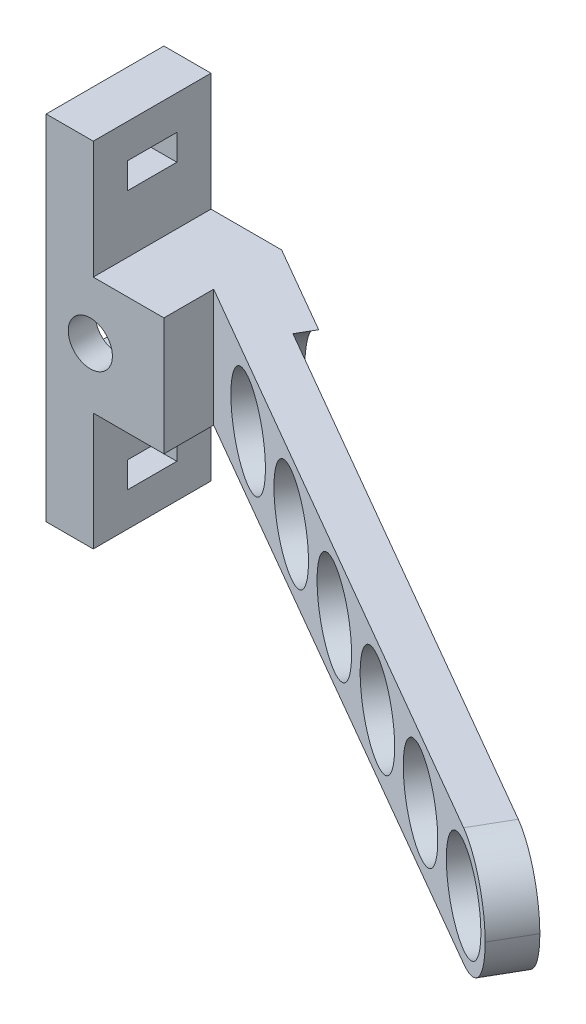
SolidWorks part; units mm, degrees
ref_plane "Front Plane" through (0, 0, 0) normal (0, 0, 1) x (1, 0, 0)
ref_plane "Top Plane" through (0, 0, 0) normal (0, 1, 0) x (1, 0, 0)
ref_plane "Right Plane" through (0, 0, 0) normal (1, 0, 0) x (0, 0, -1)
sketch "Sketch1" plane through (0, 0, 0) normal (0, 0, 1) x (1, 0, 0)
  line L1 (0, 0) -> (-12.7, 0)
  line L2 (0, 0) -> (0, 12.7)
  line L3 (0, 12.7) -> (-12.7, 12.7)
  line L4 (-12.7, 0) -> (-12.7, 12.7)
  dimension "D1" = 12.7
  dimension "D2" = 12.7
extrude "Boss-Extrude1" add sketch "Sketch1" along normal blind 12.7
sketch "Sketch2" plane through (-12.7, 0, 0) normal (-1, 0, 0) x (0, 0, 1)
  line L1 (0, 12.7) -> (12.7, 12.7)
  line L2 (0, 12.7) -> (0, 25.4)
  line L3 (0, 25.4) -> (12.7, 25.4)
  line L4 (12.7, 12.7) -> (12.7, 25.4)
  line L5 (12.7, 12.7) -> (12.7, 0) construction
  line L6 (0, 6.35) -> (12.7, 6.35) construction
  line L7 (3.683, 18.923) -> (9.017, 18.923)
  line L8 (3.683, 18.923) -> (3.683, 21.717)
  line L9 (3.683, 21.717) -> (9.017, 21.717)
  line L10 (9.017, 18.923) -> (9.017, 21.717)
  line L11 (0, 12.7) -> (0, 0) construction
  line L12 (9.017, -6.223) -> (9.017, -9.017)
  line L13 (3.683, -9.017) -> (9.017, -9.017)
  line L14 (3.683, -6.223) -> (3.683, -9.017)
  line L15 (3.683, -6.223) -> (9.017, -6.223)
  line L16 (12.7, 0) -> (12.7, -12.7)
  line L17 (0, -12.7) -> (12.7, -12.7)
  line L18 (0, 0) -> (0, -12.7)
  line L19 (0, 0) -> (12.7, 0)
  point P11 (6.35, 21.717)
  point P12 (6.35, 25.4)
  dimension "D1" = 12.7
  dimension "D2" = 6.223
  dimension "D3" = 5.334
  dimension "D4" = 2.794
extrude "Boss-Extrude2" add sketch "Sketch2" against normal blind 5.08
sketch "Sketch3" plane through (-12.7, 0, 0) normal (-1, 0, 0) x (0, 0, 1)
  line L0 (0, 25.4) -> (0, -12.7) construction
  line L1 (2.921, 1.27) -> (9.779, 1.27)
  line L2 (2.921, 1.27) -> (2.921, 11.43)
  line L3 (2.921, 11.43) -> (9.779, 11.43)
  line L4 (9.779, 1.27) -> (9.779, 11.43)
  line L5 (3.683, 18.923) -> (9.017, 18.923) construction
  point P6 (0, 6.35)
  point P7 (2.921, 6.35)
  point P10 (6.35, 18.923)
  point P11 (6.35, 11.43)
  dimension "D1" = 10.16
  dimension "D2" = 6.858
extrude "Cut-Extrude1" cut sketch "Sketch3" against normal blind 9.525
sketch "Sketch4" plane through (0, 0, 12.7) normal (0, 0, 1) x (1, 0, 0)
  line L0 (-12.7, 25.4) -> (-12.7, -12.7) construction
  circle A0 centre (-7.9375, 6.35) radius 2.3813
  point P4 (0, 0)
  point P5 (-12.7, 6.35)
  dimension "D1" = 4.7625
  dimension "D2" = 4.7625
extrude "Cut-Extrude2" cut sketch "Sketch4" against normal through all
sketch "Sketch7" plane through (0, 12.7, 0) normal (0, 1, 0) x (1, 0, 0)
  line L0 (0, -7.3323) -> (3.175, -1.8331)
  line L1 (0, -12.7) -> (0, 0) construction
  line L2 (3.175, -1.8331) -> (0, 0)
  line L3 (0, 0) -> (0, -7.3323)
  line L4 (3.175, -1.8331) -> (0, -7.3323)
  line L5 (3.175, -1.8331) -> (72.4657, -41.8381)
  line L6 (0, -7.3323) -> (69.2907, -47.3373)
  line L7 (72.4657, -41.8381) -> (69.2907, -47.3373)
  line M9 (0, -12.7) -> (0, 0)
  dimension "D1" = 30
  dimension "D2" = 6.35
  dimension "D3" = 80.01
extrude "Boss-Extrude3" add sketch "Sketch7" against normal blind 12.7 contours L7 L5 L0 L6 | L0 L2 M9
sketch "Sketch8" plane through (-3.175, 0, 5.4993) normal (-0.5, 0, 0.866) x (0.866, 0, 0.5)
  line L0 (6.35, 0) -> (6.35, 12.7) construction
  line L1 (3.6662, 0) -> (3.6662, 12.7) construction
  line L2 (13.8262, 6.35) -> (26.5262, 6.35) construction
  circle A0 centre (13.8262, 6.35) radius 5.08
  circle A1 centre (26.5262, 6.35) radius 5.08
  circle A2 centre (39.2262, 6.35) radius 5.08
  circle A3 centre (51.9262, 6.35) radius 5.08
  circle A4 centre (64.6262, 6.35) radius 5.08
  circle A5 centre (77.3262, 6.35) radius 5.08
  point P4 (6.35, 6.35)
  dimension "D1" = 10.16
  dimension "D2" = 10.16
  dimension "D3" = 12.7
extrude "Cut-Extrude5" cut sketch "Sketch8" against normal through all
fillet "Fillet2" radius 6.35 2 edges at (70.8782, 0, 44.5877) (70.8782, 12.7, 44.5877)
sketch "Sketch9" plane through (0, 0, 0) normal (0.5, 0, -0.866) x (-0.866, 0, -0.5)
  line L1 (-13.8262, -0.635) -> (-94.7488, -0.635)
  line L2 (-13.8262, -0.635) -> (-13.8262, 13.335)
  line L3 (-13.8262, 13.335) -> (-94.7488, 13.335)
  line L4 (-94.7488, -0.635) -> (-94.7488, 13.335)
  circle A0 centre (-13.8262, 6.35) radius 6.985
  circle M1 centre (-51.9262, 6.35) radius 5.08
  circle M2 centre (-64.6262, 6.35) radius 5.08
  circle M3 centre (-26.5262, 6.35) radius 5.08
  circle M4 centre (-39.2262, 6.35) radius 5.08
  circle M5 centre (-77.3262, 6.35) radius 5.08
  circle M6 centre (-13.8262, 6.35) radius 5.08
  arc M7 (-77.3262, 12.7) -> (-83.6762, 6.35) centre (-77.3262, 6.35) ccw
  arc M8 (-83.6762, 6.35) -> (-77.3262, 0) centre (-77.3262, 6.35) ccw
  line M9 (-77.3262, 0) -> (0, 0)
  line M11 (0, 12.7) -> (-77.3262, 12.7)
  dimension "D1" = 13.97
extrude "Cut-Extrude6" cut sketch "Sketch9" against normal blind 2.032 contours A0 L2 M9 M11 M6 | A0 L2 M11 M9 M6 | A0 M11 M7 M8 M9 M2 M4 M5 M3 M1
